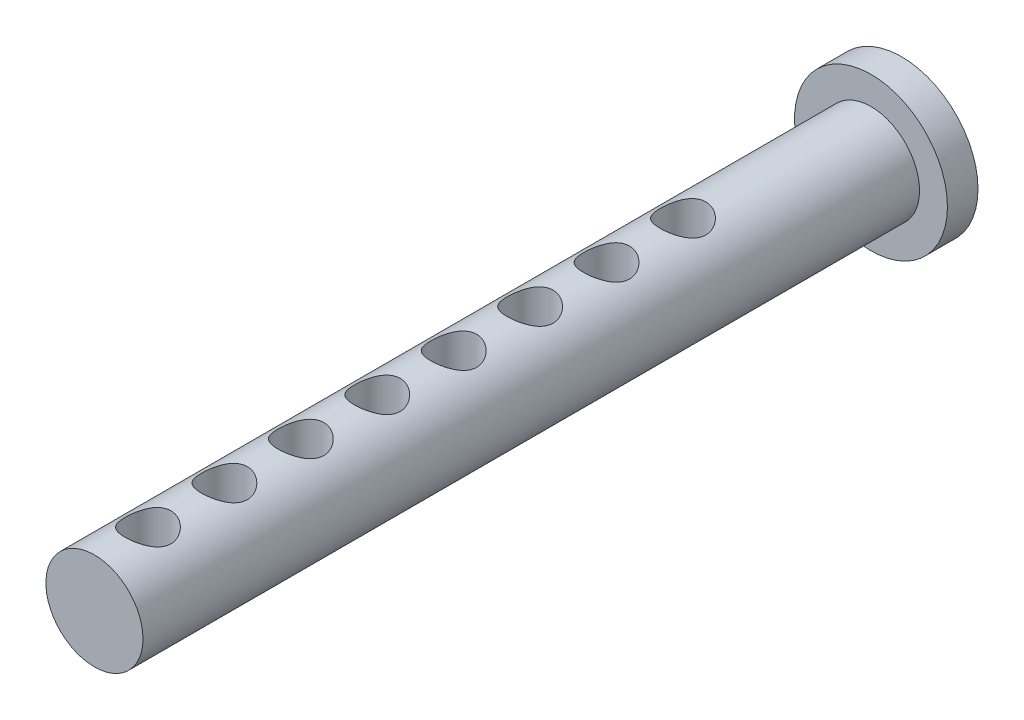
SolidWorks part; units mm, degrees
ref_plane "Front Plane" through (0, 0, 0) normal (0, 0, 1) x (1, 0, 0)
ref_plane "Top Plane" through (0, 0, 0) normal (0, 1, 0) x (1, 0, 0)
ref_plane "Right Plane" through (0, 0, 0) normal (1, 0, 0) x (0, 0, -1)
sketch "Sketch1" plane through (0, 0, 0) normal (0, 0, 1) x (1, 0, 0)
  circle A0 centre (0, 0) radius 5
  dimension "D1" = 10
extrude "Boss-Extrude1" add sketch "Sketch1" along normal blind 2
sketch "Sketch2" plane through (0, 0, 2) normal (0, 0, 1) x (1, 0, 0)
  circle A0 centre (0, 0) radius 3.175
  dimension "D1" = 6.35
extrude "Boss-Extrude2" add sketch "Sketch2" along normal blind 50.8
sketch "Sketch3" plane through (0, 0, 0) normal (0, 1, 0) x (1, 0, 0)
  line L0 (-5, -2) -> (5, -2) construction
  line L1 (0, -2) -> (0, -52.8) construction
  line L2 (-3.175, -52.8) -> (3.175, -52.8) construction
  circle A0 centre (0, -49.3) radius 1.5
  circle A1 centre (0, -44.3) radius 1.5
  circle A2 centre (0, -39.3) radius 1.5
  circle A3 centre (0, -34.3) radius 1.5
  circle A4 centre (0, -29.3) radius 1.5
  circle A5 centre (0, -24.3) radius 1.5
  circle A6 centre (0, -19.3) radius 1.5
  circle A7 centre (0, -14.3) radius 1.5
  point P10 (0, -35.8)
  point P11 (0, -37.8)
  dimension "D1" = 3
  dimension "D2" = 3.5
  dimension "D3" = 8
extrude "Cut-Extrude1" cut sketch "Sketch3" against normal through all both and the other way through all
